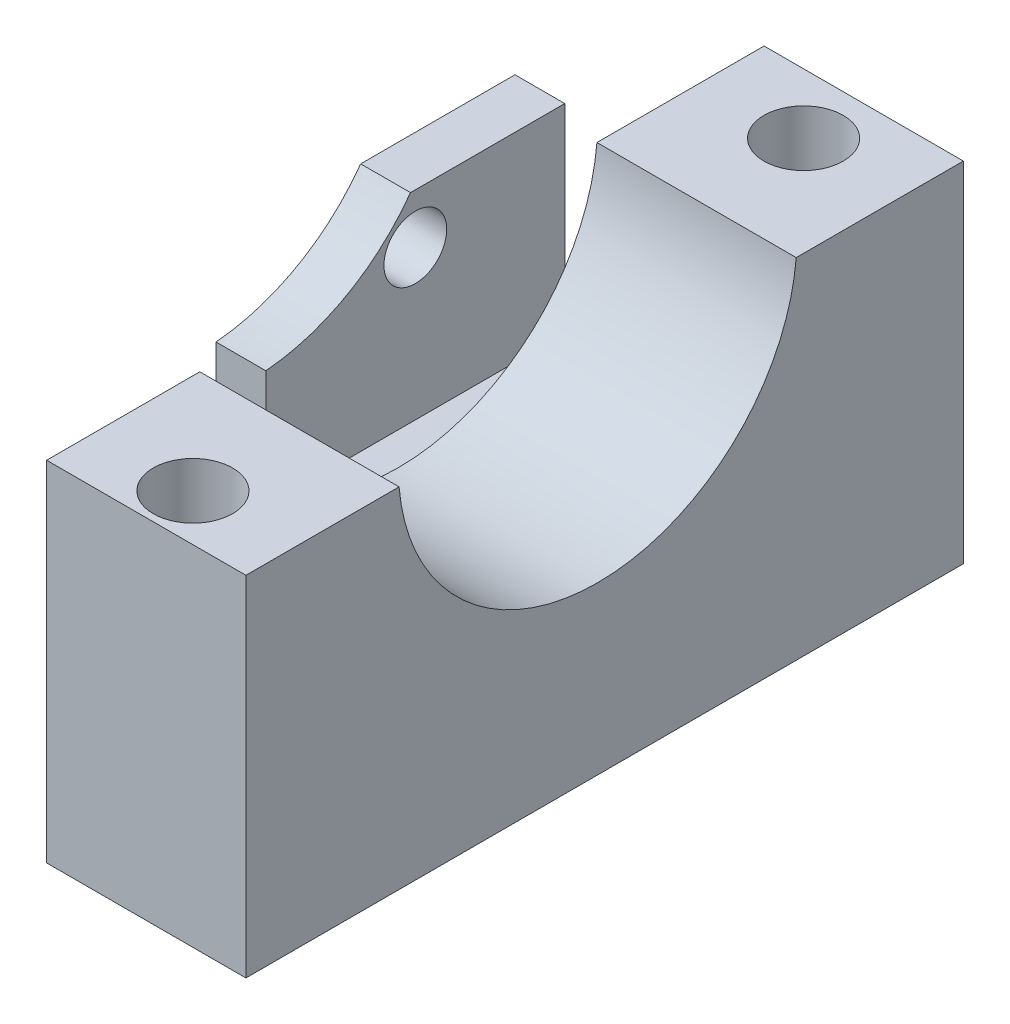
SolidWorks part; units mm, degrees
material "ABS"
ref_plane "Front Plane" through (0, 0, 0) normal (0, 0, 1) x (1, 0, 0)
ref_plane "Top Plane" through (0, 0, 0) normal (0, 1, 0) x (1, 0, 0)
ref_plane "Right Plane" through (0, 0, 0) normal (1, 0, 0) x (0, 0, -1)
sketch "Sketch1" plane through (0, 0, 0) normal (0, 1, 0) x (1, 0, 0)
  line L0 (-3.175, 9.525) -> (-3.175, -9.525)
  line L1 (-6.35, -9.525) -> (6.35, -9.525)
  line L2 (-6.35, -9.525) -> (-6.35, 9.525)
  line L3 (-6.35, 9.525) -> (6.35, 9.525)
  line L4 (6.35, -9.525) -> (6.35, 9.525)
  line L5 (-6.35, -9.525) -> (6.35, 9.525) construction
  line L6 (-6.35, 9.525) -> (6.35, -9.525) construction
  point P0 (0, 0)
  dimension "D1" = 12.7
  dimension "D2" = 3.175
  dimension "D3" = 19.05
extrude "Boss-Extrude1" add sketch "Sketch1" along normal blind 3.175 contours L1 L4 L3 L0 | L3 L2 L1 L0 region at (1.5875, 0, 0) region at (-4.7625, 0, 0)
extrude "Boss-Extrude2" add sketch "Sketch1<3>" along normal blind 12.7 from surface contours L3 L2 L1 L0 region at (-4.7625, 0, 0) starting at face at (0, 3.175, 0)
sketch "Sketch1<3>" plane through (0, 0, 0) normal (0, 1, 0) x (1, 0, 0) same geometry as "Sketch1"
sketch "Sketch2" plane through (-3.175, 0, 0) normal (1, 0, 0) x (0, 0, -1)
  line L0 (0, 15.875) -> (0, 12.7) construction
  line L1 (-9.525, 15.875) -> (9.525, 15.875) construction
  circle A0 centre (0, 12.7) radius 2
  dimension "D1" = 4
  dimension "D2" = 3.175
extrude "Cut-Extrude1" cut sketch "Sketch2" against normal through all
sketch "Sketch4" plane through (0, 0, 0) normal (0, -1, 0) x (1, 0, 0)
  line L0 (12.7, -12.7) -> (12.7, 33.02) construction
  line L1 (6.35, -12.7) -> (19.05, -12.7)
  line L2 (6.35, -12.7) -> (6.35, 33.02)
  line L3 (6.35, 33.02) -> (19.05, 33.02)
  line L4 (19.05, -12.7) -> (19.05, 33.02)
  line L5 (-3.175, -9.525) -> (6.35, -9.525) construction
  line L6 (6.35, 9.525) -> (6.35, -9.525) construction
  circle A0 centre (12.7, -6.0678) radius 1.9844 construction
  circle A1 centre (12.7, 25.6115) radius 1.9844 construction
  dimension "D2" = 3.9688
  dimension "D1" = 45.72
  dimension "D3" = 3.175
  dimension "D4" = 12.7
extrude "Boss-Extrude3" add sketch "Sketch4" against normal blind 22.225
sketch "Sketch3" plane through (-6.35, 0, 0) normal (-1, 0, 0) x (0, 0, 1)
  line L0 (0, 12.7) -> (10.6066, 23.3066) construction
  line L1 (0, 12.7) -> (9.525, 12.7) construction
  line L2 (9.525, 15.875) -> (9.525, 0) construction
  circle A0 centre (0, 12.7) radius 10 construction
  circle A1 centre (10.6066, 23.3066) radius 5 construction
  circle A2 centre (10.6066, 23.3066) radius 12.5 construction
  circle A3 centre (10.6066, 23.3066) radius 12.7
  dimension "D1" = 10
  dimension "D2" = 20
  dimension "D4" = 25
  dimension "D5" = 25.4
  dimension "D3" = 45
extrude "Cut-Extrude2" cut sketch "Sketch3" against normal through all
hole_wizard "#8 (0.199) Diameter Hole1" positions "Sketch5" profile "Sketch6" hole size "#8" standard "ANSI Inch"
sketch "Sketch5" plane through (0, 22.225, 0) normal (0, 1, 0) x (1, 0, 0)
  point P0 (12.7, 8.8685)
  point P2 (12.7, -30.0473)
sketch "Sketch6" plane through (12.7, 22.225, -8.8685) normal (1, 0, 0) x (0, 0, 1)
  line L0 (0, 0) -> (0, 62.9866)
  line L1 (0, 62.9866) -> (2.5273, 61.468)
  line L2 (2.5273, 61.468) -> (2.5273, 0)
  line L5 (2.5273, 0) -> (0, 0)
  line L10 (0, 62.9866) -> (-2.5273, 61.468) construction
  line L11 (0, -6.35) -> (0, 107.95) construction
  dimension "Hole Dia." = 5.0546
  dimension "Hole Depth" = 61.468
  dimension "Drill Angle" = 118
